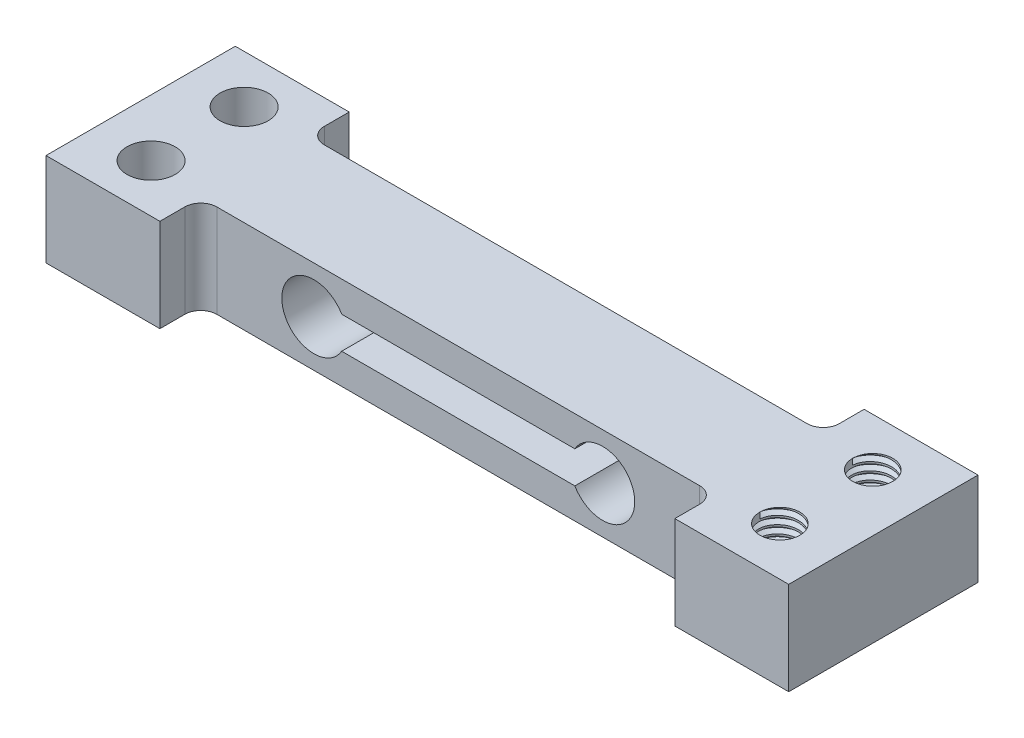
SolidWorks part; units mm, degrees
ref_plane "Front Plane" through (0, 0, 0) normal (0, 0, 1) x (1, 0, 0)
ref_plane "Top Plane" through (0, 0, 0) normal (0, 1, 0) x (1, 0, 0)
ref_plane "Right Plane" through (0, 0, 0) normal (1, 0, 0) x (0, 0, -1)
sketch "Sketch1" plane through (0, 0, 0) normal (0, 1, 0) x (1, 0, 0)
  line L1 (-16.05, -3.35) -> (16.05, -3.35)
  line L2 (-16.05, -3.35) -> (-16.05, 3.35)
  line L3 (-16.05, 3.35) -> (16.05, 3.35)
  line L4 (16.05, -3.35) -> (16.05, 3.35)
  line L5 (-16.05, -3.35) -> (16.05, 3.35) construction
  line L6 (-16.05, 3.35) -> (16.05, -3.35) construction
  line L7 (-16.05, -5.9) -> (-23.15, -5.9)
  line L8 (-16.05, -5.9) -> (-16.05, 5.9)
  line L9 (-16.05, 5.9) -> (-23.15, 5.9)
  line L10 (-23.15, -5.9) -> (-23.15, 5.9)
  line L11 (16.05, 5.9) -> (23.15, 5.9)
  line L12 (16.05, 5.9) -> (16.05, -5.9)
  line L13 (16.05, -5.9) -> (23.15, -5.9)
  line L14 (23.15, 5.9) -> (23.15, -5.9)
  point P0 (0, 0)
  dimension "D1" = 6.7
  dimension "D2" = 32.1
  dimension "D3" = 7.1
  dimension "D4" = 0
  dimension "D5" = 11.8
  dimension "D6" = 2.55
  dimension "D7" = 7.1
  dimension "D8" = 11.8
extrude "Boss-Extrude1" add sketch "Sketch1" along normal blind 5.8 contours L10 L7 L8 L2 L9 | L1 L4 L3 L2 | L14 L11 L12 L4 L13 region at (0, 0, 0) region at (-19.6, 0, 0) region at (19.6, 0, 0)
fillet "Fillet1" radius 1 4 edges at (16.05, 2.9, -3.35) (16.05, 2.9, 3.35) (-16.05, 2.9, 3.35) (-16.05, 2.9, -3.35)
sketch "Sketch2" plane through (0, 0, -3.35) normal (0, 0, -1) x (-1, 0, 0)
  line L0 (15.05, 2.9) -> (-15.05, 2.9) construction
  line L1 (15.05, 0) -> (15.05, 5.8) construction
  line L2 (-15.05, 5.8) -> (-15.05, 0) construction
  line L3 (0, 5.8) -> (0, 0) construction
  line L4 (15.05, 5.8) -> (-15.05, 5.8) construction
  line L6 (-7.5, 3.9) -> (7.5, 3.9)
  line L7 (-7.5, 3.9) -> (-7.5, 1.9)
  line L8 (-7.5, 1.9) -> (7.5, 1.9)
  line L9 (7.5, 3.9) -> (7.5, 1.9)
  circle A0 centre (9, 2.9) radius 2
  circle A1 centre (-9, 2.9) radius 2
  point P19 (-7.5, 2.9)
  dimension "D1" = 4
  dimension "D2" = 4
  dimension "D7" = 1.5
  dimension "D3" = 15
  dimension "D4" = 2
  dimension "D5" = 1
  dimension "D6" = 7.5
  dimension "D8" = 1.5
extrude "Cut-Extrude1" cut sketch "Sketch2" against normal through all contours A1 L8 A0 L6 | L8 A0 L6 L9 | L6 A0 L8 L9 | L8 A1 L6 L7 | L6 A1 L8 L7 region at (9.1207, 2.9, -3.35) region at (7.2858, 2.9, -3.35) region at (0, 2.9, -3.35) region at (-9.1207, 2.9, -3.35) region at (-7.2858, 2.9, -3.35)
sketch "Sketch3" plane through (0, 5.8, 0) normal (0, 1, 0) x (1, 0, 0)
  line L0 (19.6, 5.9) -> (19.6, -5.9) construction
  line L1 (16.05, 5.9) -> (23.15, 5.9) construction
  line L2 (16.05, -5.9) -> (23.15, -5.9) construction
  line L3 (23.15, 0) -> (-23.15, 0) construction
  line L4 (23.15, 5.9) -> (23.15, -5.9) construction
  line L5 (-23.15, -5.9) -> (-23.15, 5.9) construction
  line L6 (-19.6, 5.9) -> (-19.6, -5.9) construction
  line L7 (-16.05, 5.9) -> (-23.15, 5.9) construction
  line L8 (-16.05, -5.9) -> (-23.15, -5.9) construction
  circle A0 centre (-19.6, 2.9) radius 1.5
  circle A1 centre (-19.6, -2.9) radius 1.5
  dimension "D1" = 3
  dimension "D3" = 3
  dimension "D2" = 3
  dimension "D4" = 3
extrude "Cut-Extrude2" cut sketch "Sketch3" against normal through all
sketch "Sketch4" plane through (0, 5.8, 0) normal (0, 1, 0) x (1, 0, 0)
  line L0 (-19.6, 2.9) -> (23.15, 2.9) construction
  line L1 (23.15, 5.9) -> (23.15, -5.9) construction
  line L2 (-19.6, -2.9) -> (23.15, -2.9) construction
  line L3 (19.6, 5.9) -> (19.6, -5.9) construction
  line L4 (16.05, 5.9) -> (23.15, 5.9) construction
  line L5 (16.05, -5.9) -> (23.15, -5.9) construction
hole_wizard "M3x0.5 Tapped Hole1" positions "Sketch5" profile "Sketch6" tap size "M3x0.5" standard "ANSI Metric" end condition through all
sketch "Sketch5" plane through (0, 5.8, 0) normal (0, 1, 0) x (1, 0, 0)
  line L0 (-19.6, 2.9) -> (23.15, 2.9) construction
  line L1 (-19.6, -2.9) -> (23.15, -2.9) construction
  line L2 (19.6, 5.9) -> (19.6, -5.9) construction
  point P0 (19.5891, 2.9)
  point P4 (19.6, -2.9)
sketch "Sketch6" plane through (19.5891, 5.8, -2.9) normal (1, 0, 0) x (0, 0, 1)
  line L0 (0, 0) -> (0, 5.8)
  line L1 (0, 5.8) -> (1.25, 5.8)
  line L2 (1.25, 5.8) -> (1.25, 0)
  line L5 (1.25, 0) -> (0, 0)
  line L11 (0, -6.35) -> (0, 107.95) construction
  dimension "Thru Tap Drill Dia." = 2.5
  dimension "Thru Tap Drill Depth" = 5.8
cosmetic thread "Hole Thread1" parameters "D2"=3
cosmetic thread "Hole Thread2" parameters "D2"=3
thread "Thread1" pitch 0.5 method cut profile "Thread Profile1" start angle 0, offset 0, length 10, pitch 0.5, diameter 2.5
ref_plane "Plane1" through (18.3391, 5.8, -2.9) normal (0, 0, 1) x (-1, 0, 0)
sketch "Thread Profile1" plane through (18.3391, 5.8, -2.9) normal (0, 0, 1) x (-1, 0, 0)
  line L0 (0, 0) -> (0, 0.5) construction
  line L1 (0, 0) -> (0.2706, 0.1562)
  line L2 (0.2706, 0.1562) -> (0.2706, 0.2187)
  line L3 (0.2706, 0.2187) -> (0, 0.375)
  line L4 (0.2706, 0.1875) -> (0, 0.1875) construction
  line L11 (0, 0) -> (0, 0.375)
  point P2 (0, 0)
  dimension "Pitch" = 0.5
  dimension "Profile_Angle" = 60
  dimension "Profile_Land" = 0.0625
  dimension "Profile_Height" = 0.2706
thread "Thread2" pitch 0.5 method cut profile "Thread Profile2" start angle 0, offset 0, length 10, pitch 0.5, diameter 2.5
ref_plane "Plane2" through (18.35, 5.8, 2.9) normal (0, 0, 1) x (-1, 0, 0)
sketch "Thread Profile2" plane through (18.35, 5.8, 2.9) normal (0, 0, 1) x (-1, 0, 0)
  line L0 (0, 0) -> (0, 0.5) construction
  line L1 (0, 0) -> (0.2706, 0.1562)
  line L2 (0.2706, 0.1562) -> (0.2706, 0.2187)
  line L3 (0.2706, 0.2187) -> (0, 0.375)
  line L4 (0.2706, 0.1875) -> (0, 0.1875) construction
  line L11 (0, 0) -> (0, 0.375)
  point P2 (0, 0)
  dimension "Pitch" = 0.5
  dimension "Profile_Angle" = 60
  dimension "Profile_Land" = 0.0625
  dimension "Profile_Height" = 0.2706
